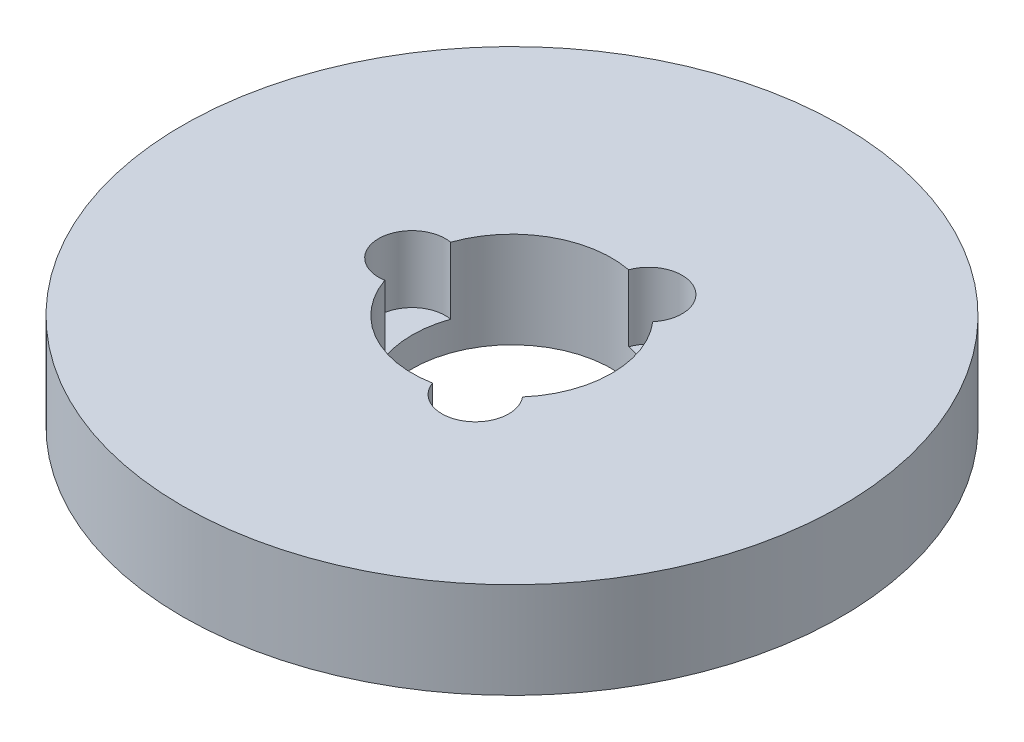
SolidWorks part; units mm, degrees
ref_plane "Front Plane" through (0, 0, 0) normal (0, 0, 1) x (1, 0, 0)
ref_plane "Top Plane" through (0, 0, 0) normal (0, 1, 0) x (1, 0, 0)
ref_plane "Right Plane" through (0, 0, 0) normal (1, 0, 0) x (0, 0, -1)
sketch "Sketch1" plane through (0, 0, 0) normal (0, 1, 0) x (1, 0, 0)
  circle A0 centre (0, 0) radius 82.5
  dimension "FLANGE_OD" = 165
extrude "Boss-Extrude1" add sketch "Sketch1" along normal blind 24
sketch "Sketch2" plane through (0, 0, 0) normal (0, 1, 0) x (1, 0, 0)
  circle A0 centre (0, 0) radius 25
  dimension "BORE_D" = 50
extrude "Cut-Extrude1" cut sketch "Sketch2" along normal through all
sketch "Sketch3" plane through (0, 24, 0) normal (0, 1, 0) x (1, 0, 0)
  circle A0 centre (0, 0) radius 25.0391 construction
  circle A1 centre (-25.0391, 0) radius 8.3737
  dimension "BOLT_D" = 16.7475
  dimension "BOLT_PCD" = 50.0781
extrude "Cut-Extrude2" cut sketch "Sketch3" against normal blind 16.688
pattern_circular "CirPattern1" count 3 over 360 about axis through (0, 0, 0) along (0, 1, 0) of "Cut-Extrude2"
